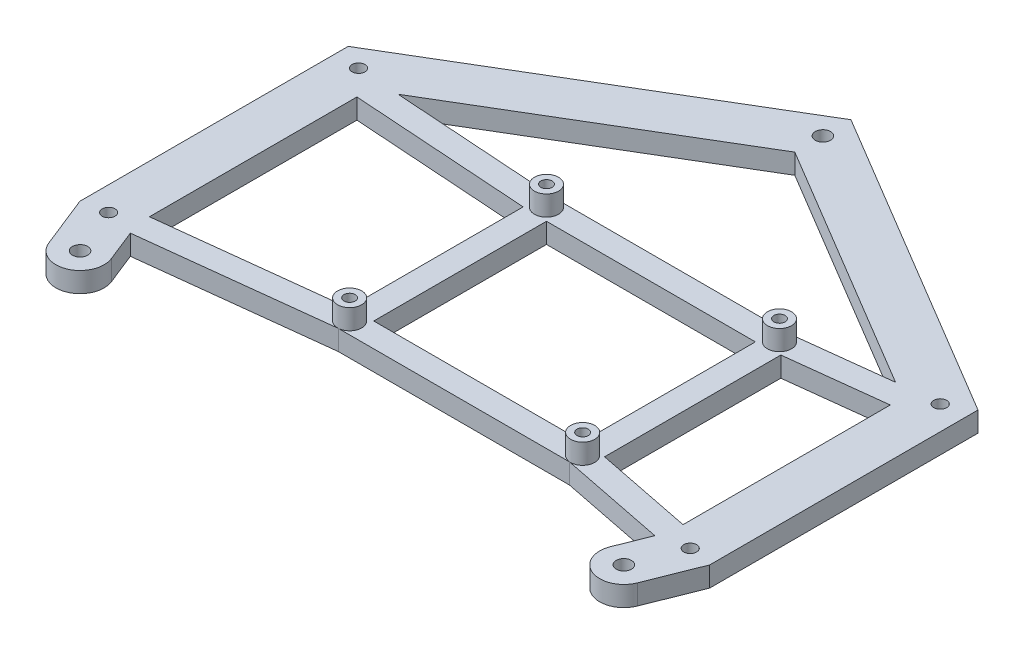
SolidWorks part; units mm, degrees
ref_plane "Front Plane" through (0, 0, 0) normal (0, 0, 1) x (1, 0, 0)
ref_plane "Top Plane" through (0, 0, 0) normal (0, 1, 0) x (1, 0, 0)
ref_plane "Right Plane" through (0, 0, 0) normal (1, 0, 0) x (0, 0, -1)
sketch "Sketch1" plane through (0, 0, 0) normal (0, 1, 0) x (1, 0, 0)
  line L0 (0, 0) -> (0, -3.85) construction
  line L1 (-76.2, 34.925) -> (76.2, 34.925)
  line L2 (-76.2, 34.925) -> (-76.2, -34.925)
  line L3 (-76.2, -34.925) -> (76.2, -34.925)
  line L4 (76.2, 34.925) -> (76.2, -34.925)
  line L5 (-76.2, 34.925) -> (76.2, -34.925) construction
  line L6 (-76.2, -34.925) -> (76.2, 34.925) construction
  line L7 (-72.39, -31.115) -> (72.39, -31.115)
  line L8 (-72.39, -31.115) -> (-72.39, 31.115)
  line L9 (-72.39, 31.115) -> (72.39, 31.115)
  line L10 (72.39, -31.115) -> (72.39, 31.115)
  line L11 (-72.39, -31.115) -> (72.39, 31.115) construction
  line L12 (-72.39, 31.115) -> (72.39, -31.115) construction
  line L13 (0, -3.85) -> (0, 74.3) construction
  line L14 (0, -3.85) -> (67.6799, -42.925) construction
  line L15 (0, -3.85) -> (-67.6799, -42.925) construction
  line L17 (-42.5, -28) -> (42.5, -28)
  line L18 (-42.5, -28) -> (-42.5, 28)
  line L19 (-42.5, 28) -> (42.5, 28)
  line L20 (42.5, -28) -> (42.5, 28)
  line L21 (-42.5, -28) -> (42.5, 28) construction
  line L22 (-42.5, 28) -> (42.5, -28) construction
  line L23 (-19, 24.5) -> (39, 24.5)
  line L24 (-19, 24.5) -> (-19, -24.5)
  line L25 (-19, -24.5) -> (39, -24.5)
  line L26 (39, 24.5) -> (39, -24.5)
  circle A1 centre (0, -3.85) radius 78.15
  point P0 (0, 0)
  point P6 (0, 0)
  point P19 (0, -3.85)
  dimension "D5" = 156.3
  dimension "D1" = 69.85
  dimension "D2" = 152.4
  dimension "D3" = 3.81
  dimension "D4" = 3.81
  dimension "D7" = 8
  dimension "D8" = 56
  dimension "D9" = 85
  dimension "D10" = 3.5
  dimension "D11" = 3.5
  dimension "D12" = 3.5
  dimension "D13" = 23.5
  dimension "D6" = 3
sketch "Sketch2" plane through (0, 0, 0) normal (0, 1, 0) x (1, 0, 0)
  line L0 (-67.6799, -42.925) -> (-72.39, -31.115) construction
  line L1 (-72.39, -31.115) -> (-72.39, 31.115) construction
  line L2 (-72.39, 31.115) -> (0, 74.3) construction
  line L3 (72.39, 31.115) -> (72.39, -31.115) construction
  line L4 (72.39, -31.115) -> (67.6799, -42.925) construction
  line L5 (0, 74.3) -> (72.39, 31.115) construction
  line L6 (-62.1068, -40.7023) -> (-66.39, -29.9627)
  line L7 (-66.39, -29.9627) -> (-66.39, 27.7078)
  line L8 (-66.39, 27.7078) -> (0, 67.3135)
  line L9 (0, 67.3135) -> (66.39, 27.7078)
  line L10 (66.39, 27.7078) -> (66.39, -29.9627)
  line L11 (66.39, -29.9627) -> (62.1068, -40.7023)
  line L12 (-73.253, -45.1477) -> (-78.39, -32.2673)
  line L13 (-78.39, -32.2673) -> (-78.39, 34.5222)
  line L14 (-78.39, 34.5222) -> (0, 81.2865)
  line L15 (0, 81.2865) -> (78.39, 34.5222)
  line L16 (78.39, 34.5222) -> (78.39, -32.2673)
  line L17 (78.39, -32.2673) -> (73.253, -45.1477)
  arc A0 (-62.1068, -40.7023) -> (-73.253, -45.1477) centre (-67.6799, -42.925) cw
  arc A1 (62.1068, -40.7023) -> (73.253, -45.1477) centre (67.6799, -42.925) ccw
  circle A2 centre (-67.6799, -42.925) radius 1.9
  circle A3 centre (-72.39, 31.115) radius 1.6
  circle A4 centre (0, 74.3) radius 1.9
  circle A5 centre (72.39, 31.115) radius 1.6
  circle A6 centre (-72.39, -31.115) radius 1.6
  circle A7 centre (72.39, -31.115) radius 1.6
  circle A8 centre (67.6799, -42.925) radius 1.9
  dimension "D3" = 3.8
  dimension "D4" = 3.2
  dimension "D1" = 6
  dimension "D2" = 6
extrude "Boss-Extrude1" add sketch "Sketch2" along normal blind 5
sketch "Sketch3" plane through (0, 0, 0) normal (0, 1, 0) x (1, 0, 0)
  circle A0 centre (-19, 24.5) radius 1.4
  circle A1 centre (-19, -24.5) radius 1.4
  circle A2 centre (39, -24.5) radius 1.4
  circle A3 centre (39, 24.5) radius 1.4
  circle A4 centre (-19, 24.5) radius 3
  circle A5 centre (39, 24.5) radius 3
  circle A6 centre (39, -24.5) radius 3
  circle A7 centre (-19, -24.5) radius 3
  dimension "D1" = 2.8
  dimension "D2" = 6
extrude "Boss-Extrude2" add sketch "Sketch3" along normal blind 10 separate body
sketch "Sketch4" plane through (0, 0, 0) normal (0, 1, 0) x (1, 0, 0)
  line L0 (-19, 24.5) -> (-66.39, 27.7078) construction
  line L1 (-19, -24.5) -> (-66.39, -29.9627) construction
  line L2 (39, 24.5) -> (66.39, 27.7078) construction
  line L3 (39, -24.5) -> (66.39, -29.9627) construction
  line L4 (-18.7974, 27.4932) -> (-66.1874, 30.701)
  line L5 (-19.3435, -21.5197) -> (-66.7335, -26.9824)
  line L6 (39.349, 21.5204) -> (66.739, 24.7282)
  line L7 (38.4132, -27.4421) -> (65.8032, -32.9047)
  line L8 (-19.2026, 21.5068) -> (-66.5926, 24.7147)
  line L9 (-18.6565, -27.4803) -> (-66.0465, -32.9429)
  line L10 (38.651, 27.4796) -> (66.041, 30.6875)
  line L11 (39.5868, -21.5579) -> (66.9768, -27.0206)
  arc A0 (-18.7974, 27.4932) -> (-19.2026, 21.5068) centre (-19, 24.5) cw
  arc A1 (-66.1874, 30.701) -> (-66.5926, 24.7147) centre (-66.39, 27.7078) ccw
  arc A2 (-19.3435, -21.5197) -> (-18.6565, -27.4803) centre (-19, -24.5) cw
  arc A3 (-66.7335, -26.9824) -> (-66.0465, -32.9429) centre (-66.39, -29.9627) ccw
  arc A4 (39.349, 21.5204) -> (38.651, 27.4796) centre (39, 24.5) cw
  arc A5 (66.739, 24.7282) -> (66.041, 30.6875) centre (66.39, 27.7078) ccw
  arc A6 (38.4132, -27.4421) -> (39.5868, -21.5579) centre (39, -24.5) cw
  arc A7 (65.8032, -32.9047) -> (66.9768, -27.0206) centre (66.39, -29.9627) ccw
  circle A8 centre (-19, -24.5) radius 1.4 construction
  circle A9 centre (39, -24.5) radius 1.4 construction
  circle A10 centre (39, 24.5) radius 1.4 construction
  circle A11 centre (-19, 24.5) radius 1.4 construction
  circle A12 centre (-19, -24.5) radius 1.4
  circle A13 centre (39, -24.5) radius 1.4
  circle A14 centre (39, 24.5) radius 1.4
  circle A15 centre (-19, 24.5) radius 1.4
  dimension "D1" = 3
  dimension "D2" = 3
extrude "Boss-Extrude3" add sketch "Sketch4" along normal blind 5
sketch "Sketch6" plane through (0, 0, 0) normal (0, 1, 0) x (1, 0, 0)
  line L8 (42, 27.5) -> (-22, 27.5)
  line L9 (42, -27.5) -> (42, 27.5)
  line L10 (-22, -27.5) -> (42, -27.5)
  line L11 (-22, 27.5) -> (-22, -27.5)
  line L12 (42, 27.5) -> (-22, 27.5)
  line L13 (42, -27.5) -> (42, 27.5)
  line L14 (-22, -27.5) -> (42, -27.5)
  line L15 (-22, 27.5) -> (-22, -27.5)
  line L16 (36, 21.5) -> (-16, 21.5)
  line L17 (36, -21.5) -> (36, 21.5)
  line L18 (-16, -21.5) -> (36, -21.5)
  line L19 (-16, 21.5) -> (-16, -21.5)
  line L20 (36, 21.5) -> (-16, 21.5)
  line L21 (36, -21.5) -> (36, 21.5)
  line L22 (-16, -21.5) -> (36, -21.5)
  line L23 (-16, 21.5) -> (-16, -21.5)
  circle A0 centre (39, -24.5) radius 1.4 construction
  circle A1 centre (39, 24.5) radius 1.4 construction
  circle A2 centre (-19, 24.5) radius 1.4 construction
  circle A3 centre (-19, -24.5) radius 1.4 construction
  circle A4 centre (39, -24.5) radius 1.4
  circle A5 centre (39, 24.5) radius 1.4
  circle A6 centre (-19, 24.5) radius 1.4
  circle A7 centre (-19, -24.5) radius 1.4
  dimension "D1" = 3
  dimension "D2" = 3
extrude "Boss-Extrude4" add sketch "Sketch6" along normal blind 5
